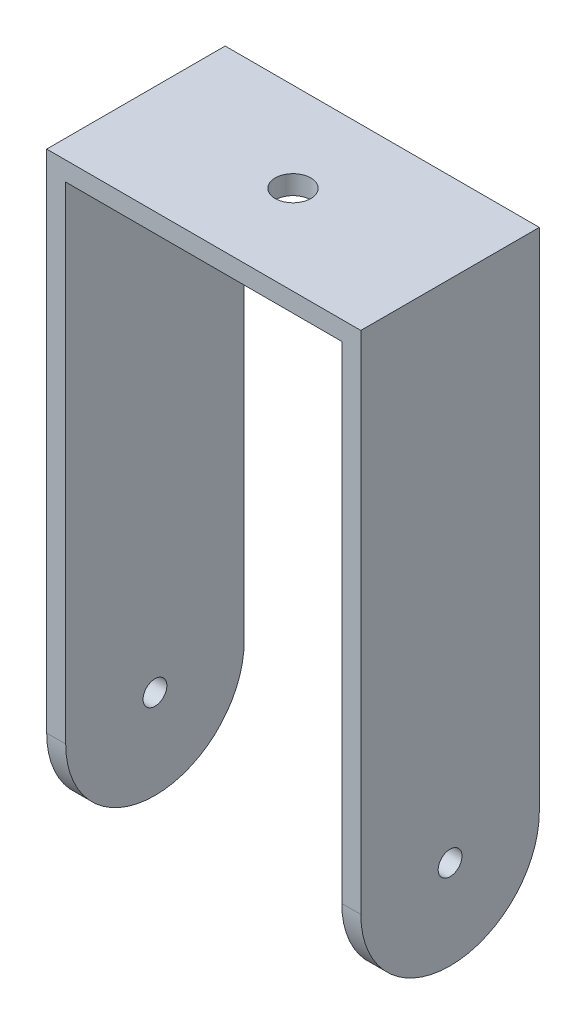
SolidWorks part; units mm, degrees
ref_plane "Front Plane" through (0, 0, 0) normal (0, 0, 1) x (1, 0, 0)
ref_plane "Top Plane" through (0, 0, 0) normal (0, 1, 0) x (1, 0, 0)
ref_plane "Right Plane" through (0, 0, 0) normal (1, 0, 0) x (0, 0, -1)
sketch "Sketch1" plane through (0, 0, 0) normal (0, 0, 1) x (1, 0, 0)
  line L0 (124, -250) -> (132, -250)
  line L1 (0, 0) -> (132, 0)
  line L2 (0, 0) -> (0, -250)
  line L3 (0, -250) -> (8, -250)
  line L4 (132, 0) -> (132, -250)
  line L5 (8, -8) -> (124, -8)
  line L6 (8, -8) -> (8, -250)
  line L8 (124, -8) -> (124, -250)
  dimension "D1" = 250
  dimension "D2" = 132
  dimension "D3" = 8
  dimension "D4" = 8
  dimension "D5" = 8
extrude "Boss-Extrude1" add sketch "Sketch1" along normal blind 75
sketch "Sketch2" plane through (0, 0, 0) normal (0, 1, 0) x (1, 0, 0)
  line L0 (132, -75) -> (132, 0) construction
  line L1 (132, -75) -> (0, -75) construction
  circle A1 centre (66, -37.5) radius 7.5
  point P8 (82.8137, -37.5722)
  dimension "D1" = 66
  dimension "D2" = 37.5
extrude "Cut-Extrude1" cut sketch "Sketch2" against normal blind 8
sketch "Sketch3" plane through (132, 0, 0) normal (1, 0, 0) x (0, 0, -1)
  line L0 (-75, -250) -> (0, -250) construction
  line L1 (-75, -250) -> (-75, 0) construction
  circle A0 centre (-37.5, -212.5) radius 5
  dimension "D3" = 10
  dimension "D1" = 37.5
  dimension "D2" = 37.5
extrude "Cut-Extrude2" cut sketch "Sketch3" against normal blind 134
fillet "Fillet1" radius 37.5 4 edges at (128, -250, 75) (4, -250, 75) (4, -250, 0) (128, -250, 0)
